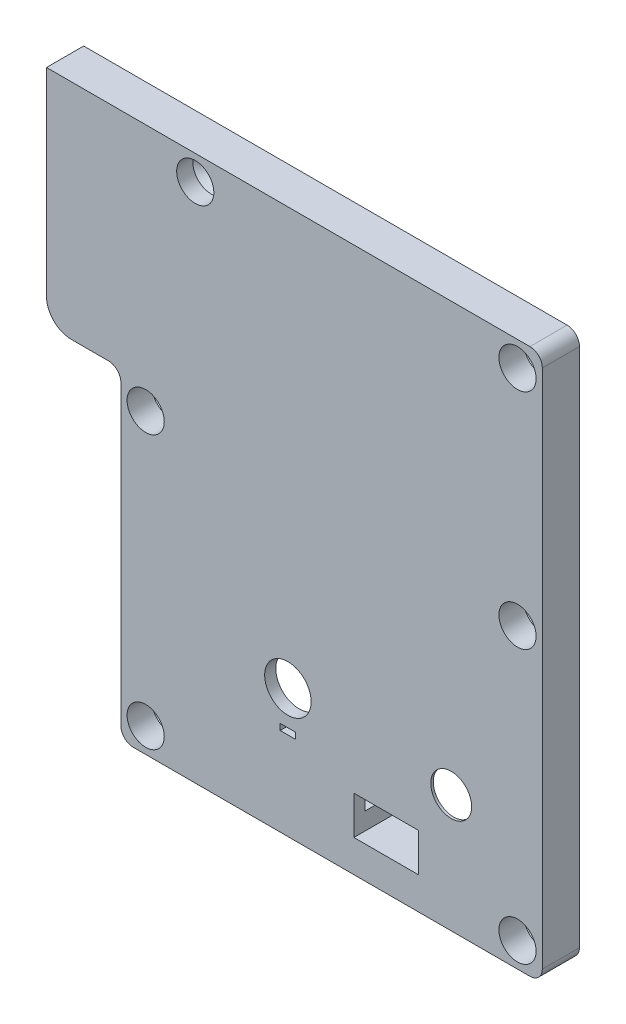
SolidWorks part; units mm, degrees
ref_plane "前视基准面" through (0, 0, 0) normal (0, 0, 1) x (1, 0, 0)
ref_plane "上视基准面" through (0, 0, 0) normal (0, 1, 0) x (1, 0, 0)
ref_plane "右视基准面" through (0, 0, 0) normal (1, 0, 0) x (0, 0, -1)
sketch "草图1" plane through (0, 0, 0) normal (0, 0, 1) x (1, 0, 0)
  line L0 (0, 0) -> (68, 0)
  line L1 (68, 0) -> (68, 88)
  line L2 (68, 88) -> (8, 88)
  line L3 (8, 88) -> (8, 52)
  line L4 (8, 52) -> (0, 52)
  line L5 (0, 52) -> (0, 0)
  line L6 (2.2, 49.8) -> (2.2, 2.2)
  line L7 (2.2, 2.2) -> (65.8, 2.2)
  line L8 (65.8, 2.2) -> (65.8, 85.8)
  line L9 (65.8, 85.8) -> (10.2, 85.8)
  line L10 (10.2, 85.8) -> (10.2, 49.8)
  line L11 (10.2, 49.8) -> (2.2, 49.8)
  line L12 (8, 44) -> (8, 8)
  line L13 (8, 8) -> (60, 8)
  line L14 (60, 8) -> (60, 80)
  line L15 (60, 80) -> (16, 80)
  line L16 (16, 80) -> (16, 44)
  line L17 (16, 44) -> (8, 44)
  dimension "D1" = 8
  dimension "D2" = 68
  dimension "D3" = 36
  dimension "D4" = 88
  dimension "D5" = 2.2
  dimension "D6" = 8
extrude "凸台-拉伸1" add sketch "草图1" against normal blind 6 contours L5 L0 L1 L2 L3 L4
extrude "凸台-拉伸4" add sketch "草图1<2>" against normal blind 6.8 contours L10 L11 L6 L7 L8 L9 region at (6.2, 48.7496, 0)
sketch "草图1<2>" plane through (0, 0, 0) normal (0, 0, 1) x (1, 0, 0) same geometry as "草图1"
extrude "切除-拉伸6" cut sketch "草图1<5>" against normal through all from offset 1.8 contours L16 L17 L12 L13 L14 L15 region at (35.8333, 42.5, 0) offset against normal yes
sketch "草图1<5>" plane through (0, 0, 0) normal (0, 0, 1) x (1, 0, 0) same geometry as "草图1"
fillet "圆角1" radius 2 8 edges at (68, 0, -3) (0, 0, -3) (68, 88, -3) (2.2, 2.2, -6.4) (65.8, 2.2, -6.4) (65.8, 85.8, -6.4) (10.2, 85.8, -6.4) (2.2, 49.8, -6.4)
sketch "草图4" plane through (0, 0, 0) normal (0, 0, 1) x (1, 0, 0)
  line L0 (61, 81) -> (67, 81)
  line L1 (9, 87) -> (15, 87)
  line L2 (9, 87) -> (9, 81)
  line L3 (9, 81) -> (15, 81)
  line L4 (15, 87) -> (15, 81)
  line L5 (9, 87) -> (15, 81) construction
  line L6 (9, 81) -> (15, 87) construction
  line L7 (67, 87) -> (67, 81)
  line L8 (61, 87) -> (61, 81)
  line L9 (61, 87) -> (67, 81) construction
  line L10 (61, 81) -> (67, 87) construction
  line L11 (61, 87) -> (67, 87)
  line L12 (61, 1) -> (67, 1)
  line L13 (67, 7) -> (67, 1)
  line L14 (61, 7) -> (61, 1)
  line L15 (61, 7) -> (67, 1) construction
  line L16 (61, 1) -> (67, 7) construction
  line L17 (61, 7) -> (67, 7)
  line L18 (1, 45) -> (7, 45)
  line L19 (7, 51) -> (7, 45)
  line L20 (1, 51) -> (1, 45)
  line L21 (1, 51) -> (7, 45) construction
  line L22 (1, 45) -> (7, 51) construction
  line L23 (1, 51) -> (7, 51)
  line L24 (1, 1) -> (7, 1)
  line L25 (7, 7) -> (7, 1)
  line L26 (1, 7) -> (1, 1)
  line L27 (1, 7) -> (7, 1) construction
  line L28 (1, 1) -> (7, 7) construction
  line L29 (1, 7) -> (7, 7)
  line L30 (61, 51) -> (67, 51)
  line L31 (61, 51) -> (67, 45) construction
  line L32 (67, 51) -> (67, 45)
  line L33 (61, 45) -> (67, 45)
  line L34 (61, 45) -> (67, 51) construction
  line L35 (61, 51) -> (61, 45)
  line L36 (2, 0) -> (66, 0) construction
  line L37 (0, 52) -> (0, 2) construction
  line L38 (66, 88) -> (8, 88) construction
  line L39 (8, 88) -> (8, 52) construction
  circle A0 centre (12, 84) radius 1.6
  circle A1 centre (64, 84) radius 1.6
  circle A2 centre (64, 4) radius 1.6
  circle A3 centre (4, 48) radius 1.6
  circle A4 centre (4, 4) radius 1.6
  circle A5 centre (64, 48) radius 1.6
  circle A6 centre (12, 84) radius 3
  circle A7 centre (64, 84) radius 3
  circle A8 centre (4, 48) radius 3
  circle A9 centre (64, 48) radius 3
  circle A10 centre (4, 4) radius 3
  circle A11 centre (64, 4) radius 3
  dimension "D1" = 3.2
  dimension "D8" = 44
  dimension "D9" = 36
  dimension "D10" = 52
  dimension "D11" = 60
  dimension "D12" = 60
  dimension "D13" = 4
  dimension "D14" = 4
  dimension "D15" = 4
  dimension "D16" = 4
  dimension "D2" = 6
  dimension "D3" = 6
  dimension "D4" = 6
  dimension "D5" = 6
  dimension "D6" = 6
  dimension "D7" = 6
extrude "切除-拉伸4" cut sketch "草图4" against normal through all and the other way through all contours A0 | A1 | A5 | A3 | A4 | A2
sketch "草图5" plane through (0, 0, 0) normal (0, 0, 1) x (1, 0, 0)
  line L0 (39.8, -18.5) -> (45.8, -18.5) construction
  line L1 (25.7, -15.2) -> (28.2, -15.2)
  line L2 (25.7, -15.2) -> (25.7, -14.2)
  line L3 (25.7, -14.2) -> (28.2, -14.2)
  line L4 (28.2, -15.2) -> (28.2, -14.2)
  line L5 (25.7, -15.2) -> (28.2, -14.2) construction
  line L6 (25.7, -14.2) -> (28.2, -15.2) construction
  line L7 (37.6, -11.4) -> (48, -11.4)
  line L8 (37.6, -11.4) -> (37.6, -5.2)
  line L9 (37.6, -5.2) -> (48, -5.2)
  line L10 (48, -11.4) -> (48, -5.2)
  line L11 (37.6, -11.4) -> (48, -5.2) construction
  line L12 (37.6, -5.2) -> (48, -11.4) construction
  line L13 (39.8, -16.7) -> (45.8, -16.7)
  line L14 (39.8, -20.3) -> (45.8, -20.3)
  line L15 (48.6, -23.8) -> (58, -23.8)
  line L16 (48.6, -23.8) -> (48.6, -12.4)
  line L17 (48.6, -12.4) -> (58, -12.4)
  line L18 (58, -23.8) -> (58, -12.4)
  line L19 (8, -27.8) -> (60, -27.8)
  line L20 (8, -27.8) -> (8, -4)
  line L21 (8, -4) -> (60, -4)
  line L22 (60, -27.8) -> (60, -4)
  line L23 (2, 0) -> (66, 0) construction
  line L24 (0, 52) -> (0, 2) construction
  line L25 (2, 0) -> (66, 0) construction
  line L26 (37.6, 5.2) -> (48, 11.4) construction
  line L27 (37.6, 11.4) -> (48, 5.2) construction
  line L28 (25.7, 14.2) -> (28.2, 15.2) construction
  line L29 (25.7, 15.2) -> (28.2, 14.2) construction
  line L34 (58, 23.8) -> (58, 12.4)
  line L35 (48.6, 12.4) -> (58, 12.4)
  line L36 (48.6, 23.8) -> (48.6, 12.4)
  line L37 (48.6, 23.8) -> (58, 23.8)
  line L38 (48, 11.4) -> (48, 5.2)
  line L39 (37.6, 5.2) -> (48, 5.2)
  line L40 (37.6, 11.4) -> (37.6, 5.2)
  line L41 (37.6, 11.4) -> (48, 11.4)
  line L42 (28.2, 15.2) -> (28.2, 14.2)
  line L43 (25.7, 14.2) -> (28.2, 14.2)
  line L44 (25.7, 15.2) -> (25.7, 14.2)
  line L45 (25.7, 15.2) -> (28.2, 15.2)
  line L46 (39.8, 18.5) -> (45.8, 18.5) construction
  line L47 (39.8, 16.7) -> (45.8, 16.7)
  line L48 (39.8, 20.3) -> (45.8, 20.3)
  circle A0 centre (26.95, -20.7) radius 3.75
  arc A1 (39.8, -16.7) -> (39.8, -20.3) centre (39.8, -18.5) ccw
  arc A2 (45.8, -20.3) -> (45.8, -16.7) centre (45.8, -18.5) ccw
  circle A3 centre (53.3, -19) radius 3.3
  circle A4 centre (53.3, 19) radius 3.3
  circle A5 centre (26.95, 20.7) radius 3.75
  arc A6 (39.8, 16.7) -> (39.8, 20.3) centre (39.8, 18.5) cw
  arc A7 (45.8, 20.3) -> (45.8, 16.7) centre (45.8, 18.5) cw
  point P2 (26.95, -14.7)
  point P8 (42.8, -8.3)
  point P14 (42.8, -18.5)
  point P25 (53.3, -23.8)
  point P52 (42.8, 18.5)
  point P58 (42.8, 8.3)
  point P59 (26.95, 14.7)
  dimension "D1" = 7.5
  dimension "D9" = 1.8
  dimension "D12" = 6.6
  dimension "D2" = 1
  dimension "D3" = 2.5
  dimension "D4" = 5.5
  dimension "D5" = 10.4
  dimension "D6" = 6.2
  dimension "D7" = 5.3
  dimension "D8" = 6
  dimension "D10" = 9.4
  dimension "D11" = 11.4
  dimension "D13" = 4.8
  dimension "D14" = 0.6
  dimension "D15" = 1
  dimension "D16" = 9.4
  dimension "D17" = 2.8
  dimension "D18" = 52
  dimension "D19" = 2
  dimension "D20" = 1.2
  dimension "D21" = 4
  dimension "D22" = 23.8
  dimension "D23" = 23.8
  dimension "D24" = 4
  dimension "D25" = 8
extrude "切除-拉伸5" cut sketch "草图5" against normal through all contours A5 | L41 L40 L39 L38 | L45 L44 L43 L42 | L35 L34 L37 L36 region at (42.8, 8.3, 0) region at (26.95, 14.7, 0) region at (26.95, 20.7, 0)
extrude "凸台-拉伸5" add sketch "草图5<3>" against normal blind 0.4 contours L37 L36 L35 L34 A4 region at (57.8522, 18.1, 0)
sketch "草图5<3>" plane through (0, 0, 0) normal (0, 0, 1) x (1, 0, 0) same geometry as "草图5"
sketch "草图6" plane through (0, 0, 0) normal (0, 0, 1) x (1, 0, 0)
  line L1 (8, 52) -> (-12, 52)
  line L2 (8, 52) -> (8, 88)
  line L3 (8, 88) -> (-12, 88)
  line L4 (-12, 52) -> (-12, 88)
  dimension "D1" = 20
extrude "凸台-拉伸7" add sketch "草图6" against normal blind 6
fillet "圆角2" radius 2 1 edges at (0, 52, -3)
fillet "圆角3" radius 4 1 edges at (-12, 52, -3)
sketch "草图7" plane through (-12, 0, 0) normal (-1, 0, 0) x (0, 0, 1)
  line L0 (-6, 88) -> (0, 88) construction
  circle A0 centre (-3, 82) radius 1.4
  circle A1 centre (-3, 62) radius 1.4
  dimension "D1" = 2.8
  dimension "D3" = 20
  dimension "D2" = 6
extrude "切除-拉伸7" cut sketch "草图7" against normal blind 20
extrude "切除-拉伸8" cut sketch "草图4<3>" against normal blind 4 contours A6 A0 | A7 A1 | A8 A3 | A9 A5 | A10 A4 | A11 A2 region at (61.9387, 81.9387, 0) region at (14.0613, 86.0613, 0) region at (61.9387, 1.9387, 0) region at (1.9387, 45.9387, 0) region at (1.9387, 1.9387, 0) region at (66.0613, 50.0613, 0)
sketch "草图4<3>" plane through (0, 0, 0) normal (0, 0, 1) x (1, 0, 0) same geometry as "草图4"
sketch "草图8" plane through (0, 0, 0) normal (0, -1, 0) x (1, 0, 0)
  line L0 (68, 0) -> (68, -6) construction
  line L1 (0, -6) -> (0, 0) construction
  circle A0 centre (58, -3) radius 1.4
  circle A1 centre (10, -3) radius 1.4
  circle A2 centre (34, -3) radius 1.4
  dimension "D1" = 2.8
  dimension "D2" = 10
  dimension "D3" = 10
  dimension "D4" = 48
  dimension "D5" = 24
extrude "切除-拉伸9" cut sketch "草图8" against normal blind 7
chamfer "倒角1" distance 1.4 angle 45 6 edges at (65.6, 4, -4) (5.6, 4, -4) (5.6, 48, -4) (65.6, 48, -4) (65.6, 84, -4) (15, 84, -4)
